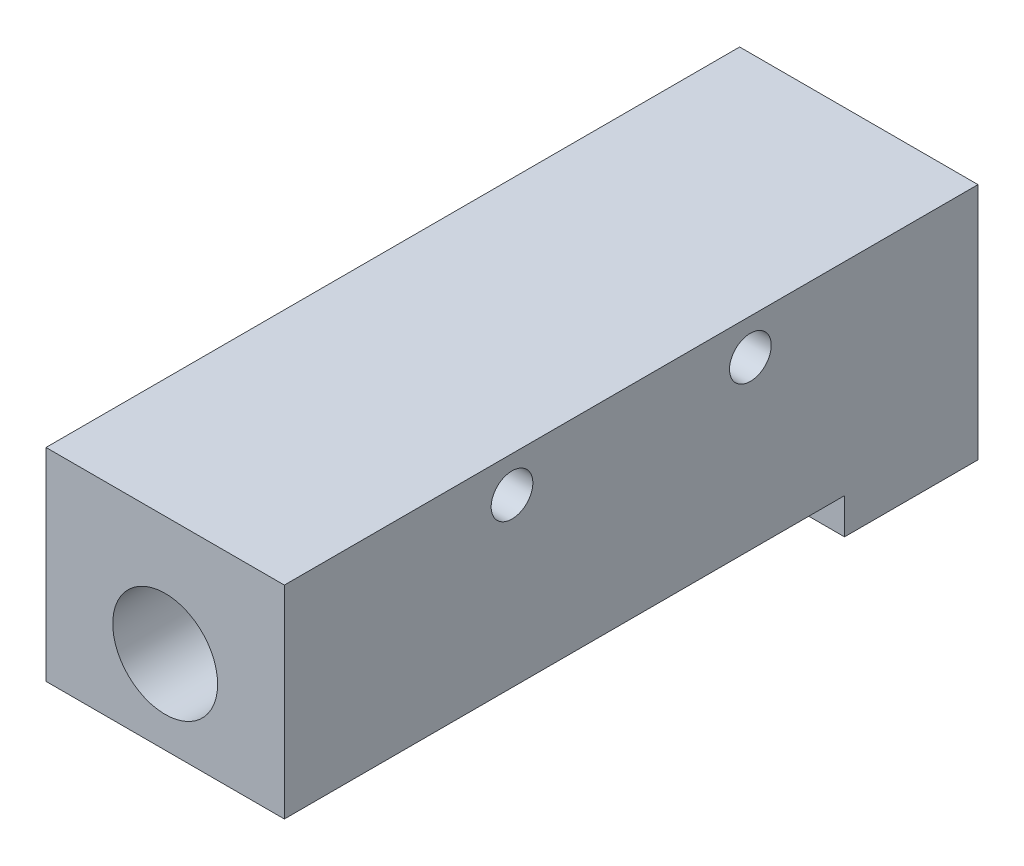
SolidWorks part; units mm, degrees
material "6063-T5"
ref_plane "Piano frontale" through (0, 0, 0) normal (0, 0, 1) x (1, 0, 0)
ref_plane "Piano superiore" through (0, 0, 0) normal (0, 1, 0) x (1, 0, 0)
ref_plane "Piano destro" through (0, 0, 0) normal (1, 0, 0) x (0, 0, -1)
sketch "Schizzo1" plane through (0, 0, 0) normal (0, 0, 1) x (1, 0, 0)
  line L1 (10, -10) -> (-10, -10)
  line L2 (10, -10) -> (10, 10)
  line L3 (10, 10) -> (-10, 10)
  line L4 (-10, -10) -> (-10, 10)
  line L5 (10, -10) -> (-10, 10) construction
  line L6 (10, 10) -> (-10, -10) construction
  point P0 (0, 0)
  dimension "D1" = 20
  dimension "D2" = 20
extrude "Estrusione-Estrusione1" add sketch "Schizzo1" against normal blind 58.2
sketch "Schizzo2" plane through (0, 0, -58.2) normal (0, 0, -1) x (-1, 0, 0)
  circle A0 centre (0, 0) radius 3
  dimension "D1" = 6
extrude "Taglio-Estrusione1" cut sketch "Schizzo2" against normal through all
sketch "Schizzo3" plane through (0, 0, -58.2) normal (0, 0, -1) x (-1, 0, 0)
  circle A0 centre (0, 0) radius 6
  dimension "D1" = 12
extrude "Taglio-Estrusione2" cut sketch "Schizzo3" against normal blind 13
sketch "Schizzo4" plane through (10, 0, 0) normal (1, 0, 0) x (0, 0, -1)
  line L0 (0, 7) -> (58.2, 7) construction
  line L1 (0, -10) -> (0, 10) construction
  line L2 (58.2, -10) -> (58.2, 10) construction
  line L3 (58.2, 10) -> (0, 10) construction
  line L4 (29.1, 10) -> (29.1, -10) construction
  line L5 (58.2, -10) -> (0, -10) construction
  circle A0 centre (19.1, 7) radius 1.75
  circle A1 centre (39.1, 7) radius 1.75
  dimension "D2" = 3.5
  dimension "D1" = 3
  dimension "D3" = 10
extrude "Taglio-Estrusione3" cut sketch "Schizzo4" against normal through all
hole_wizard "Foro filettato G1/8-1" positions "Schizzo8" profile "Schizzo7" tap size "G1/8" standard "BSI"
sketch "Schizzo8" plane through (0, 0, 0) normal (0, 0, 1) x (1, 0, 0)
  point P0 (0, 0)
sketch "Schizzo7" plane through (0, 0, 0) normal (1, 0, 0) x (0, -1, 0)
  line L0 (0, 0) -> (0, 12.6438)
  line L1 (0, 12.6438) -> (4.4, 10)
  line L2 (4.4, 10) -> (4.4, 0)
  line L5 (4.4, 0) -> (0, 0)
  line L10 (0, 12.6438) -> (-4.4, 10) construction
  line L11 (0, -6.35) -> (0, 107.95) construction
  dimension "Tap Drill Dia." = 8.8
  dimension "Tap Drill Depth" = 10
  dimension "Drill Angle" = 118
sketch "Schizzo10" plane through (10, 0, 0) normal (1, 0, 0) x (0, 0, -1)
  line L0 (0, -7) -> (47, -7)
  line L1 (0, -10) -> (0, 10) construction
  line L2 (47, -7) -> (47, -10)
  line L3 (58.2, -10) -> (0, -10) construction
  dimension "D1" = 47
  dimension "D2" = 3
extrude "Taglio-Estrusione5" cut sketch "Schizzo10" against normal through all and the other way through all flip side to cut
